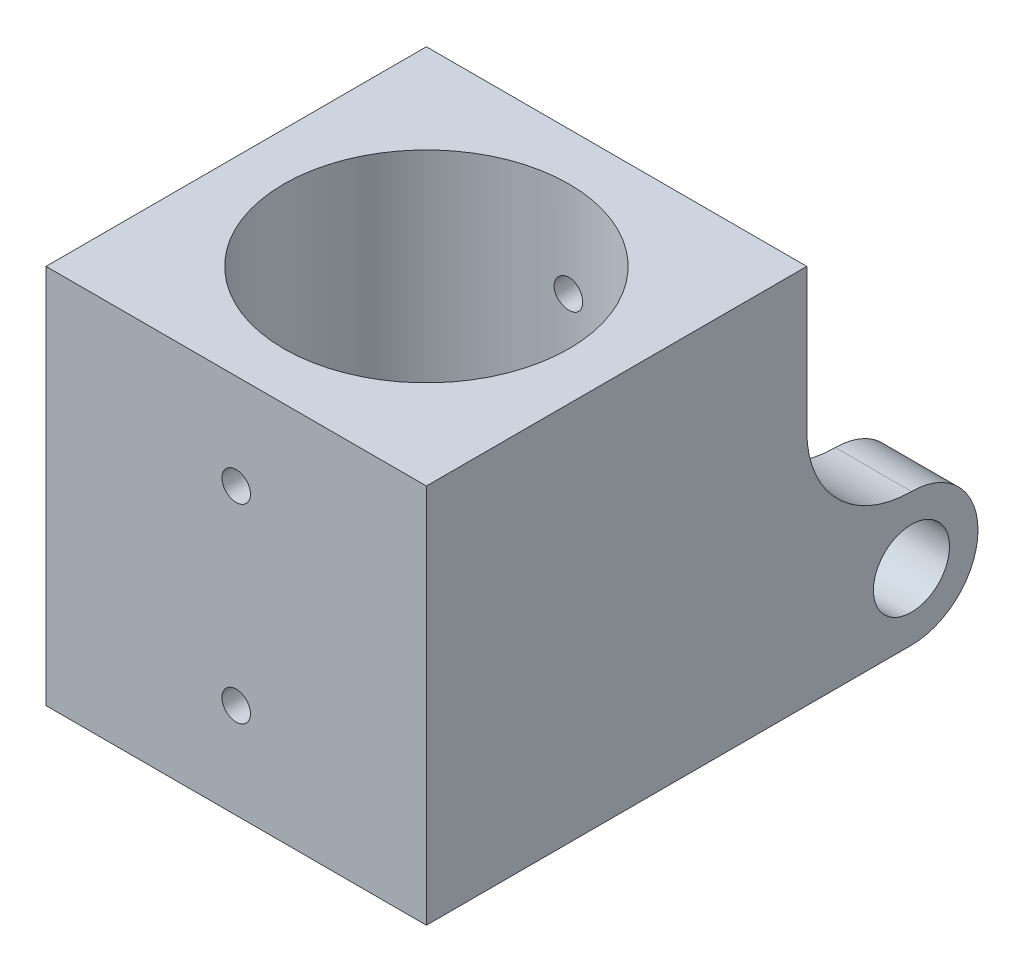
SolidWorks part; units mm, degrees
ref_plane "前基準面" through (0, 0, 0) normal (0, 0, 1) x (1, 0, 0)
ref_plane "上基準面" through (0, 0, 0) normal (0, 1, 0) x (1, 0, 0)
ref_plane "右基準面" through (0, 0, 0) normal (1, 0, 0) x (0, 0, -1)
sketch "草圖1" plane through (0, 0, 0) normal (0, 1, 0) x (1, 0, 0)
  line L1 (-20, 20) -> (20, 20)
  line L2 (-20, 20) -> (-20, -20)
  line L3 (-20, -20) -> (20, -20)
  line L4 (20, 20) -> (20, -20)
  line L5 (-20, 20) -> (20, -20) construction
  line L6 (-20, -20) -> (20, 20) construction
  circle A0 centre (0, 0) radius 15
  point P0 (0, 0)
  dimension "D3" = 30
  dimension "D1" = 40
  dimension "D2" = 40
extrude "填料-伸長1" add sketch "草圖1" along normal blind 40
sketch "草圖2" plane through (0, 0, 20) normal (0, 0, 1) x (1, 0, 0)
  line L0 (-20, 40) -> (20, 40) construction
  circle A0 centre (0, 10) radius 1.5
  circle A1 centre (0, 30) radius 1.5
  dimension "D1" = 3
  dimension "D2" = 10
  dimension "D3" = 10
extrude "除料-伸長1" cut sketch "草圖2" against normal through all
sketch "草圖3" plane through (20, 0, 0) normal (1, 0, 0) x (0, 0, -1)
  line L4 (20, 0) -> (20, 14)
  line L5 (20, 40) -> (20, 0) construction
  line L6 (20, 14) -> (31, 14)
  line L8 (31, 0) -> (20, 0)
  arc A2 (31, 0) -> (31, 14) centre (31, 7) ccw
  circle A3 centre (31, 7) radius 4
  dimension "D4" = 7
  dimension "D6" = 8
  dimension "D5" = 11
extrude "填料-伸長2" add sketch "草圖3" against normal blind 8
fillet "圓角1" radius 11 1 edges at (16, 14, -20)
